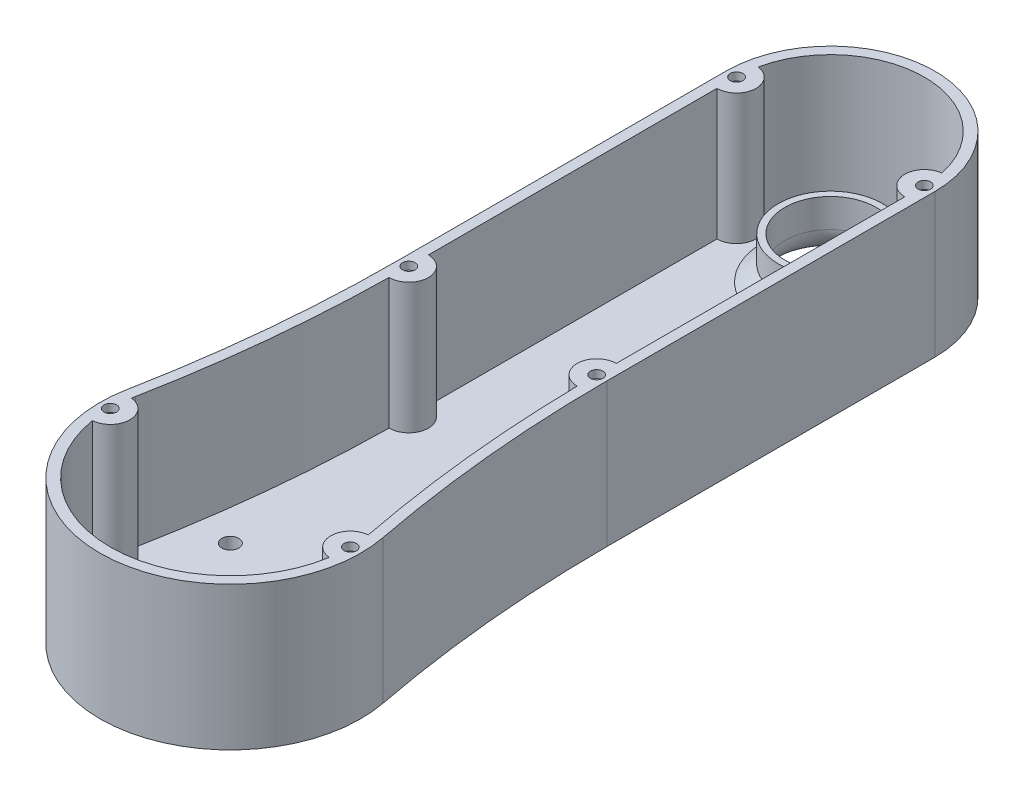
SolidWorks part; units mm, degrees
ref_plane "前视基准面" through (0, 0, 0) normal (0, 0, 1) x (1, 0, 0)
ref_plane "上视基准面" through (0, 0, 0) normal (0, 1, 0) x (1, 0, 0)
ref_plane "右视基准面" through (0, 0, 0) normal (1, 0, 0) x (0, 0, -1)
other "Configuration Table"
sketch "草图1" plane through (0, 0, 0) normal (0, 1, 0) x (1, 0, 0)
  line L0 (0, 0) -> (0, 50000) construction
  line L4 (40, 230) -> (40, 104.4031)
  line L6 (-40, 230) -> (-40, 104.4031)
  arc A8 (-49.0909, 9.4912) -> (49.0909, 9.4912) centre (0, 0) ccw
  arc A9 (40, 230) -> (-40, 230) centre (0, 230) ccw
  arc A10 (40, 104.4031) -> (49.0909, 9.4912) centre (540, 104.4031) ccw
  arc A11 (-40, 104.4031) -> (-49.0909, 9.4912) centre (-540, 104.4031) cw
  point P10 (0, 30)
  point P11 (40, 30)
  point P14 (-40, 30)
  dimension "D1" = 100
  dimension "D4" = 40
  dimension "D5" = 500
  dimension "D2" = 40
  dimension "D3" = 200
extrude "凸台-拉伸1" add sketch "草图1" along normal blind 5
sketch "草图2" plane through (0, 5, 0) normal (0, 1, 0) x (1, 0, 0)
  circle A0 centre (28.2843, 28.2843) radius 3.25
  circle A1 centre (28.2843, -28.2843) radius 3.25
  circle A2 centre (-28.2843, -28.2843) radius 3.25
  circle A3 centre (-28.2843, 28.2843) radius 3.25
  point P12 (0, 0)
  dimension "D1" = 6.5
  dimension "D2" = 4
extrude "切除-拉伸1" cut sketch "草图2" against normal blind 5
sketch "草图3" plane through (0, 5, 0) normal (0, 1, 0) x (1, 0, 0)
  line L9 (40, 104.4031) -> (40, 230)
  line L10 (-40, 230) -> (-40, 104.4031)
  line L11 (36, 104.4031) -> (36, 230)
  line L12 (-36, 230) -> (-36, 104.4031)
  line L13 (36, 111.9031) -> (36, 222.5)
  line L14 (-36, 222.5) -> (-36, 111.9031)
  line L15 (0, 230) -> (0, -49770) construction
  line L16 (-36, 230) -> (-36, 104.4031) construction
  line L17 (36, 104.4031) -> (36, 230) construction
  arc A12 (40, 230) -> (-40, 230) centre (0, 230) ccw
  arc A13 (-49.0909, 9.4912) -> (-40, 104.4031) centre (-540, 104.4031) ccw
  arc A14 (-49.0909, 9.4912) -> (49.0909, 9.4912) centre (0, 0) ccw
  arc A15 (40, 104.4031) -> (49.0909, 9.4912) centre (540, 104.4031) ccw
  arc A16 (-45.1636, 8.7319) -> (45.1636, 8.7319) centre (0, 0) ccw
  arc A17 (-45.1636, 8.7319) -> (-36, 104.4031) centre (-540, 104.4031) ccw
  arc A18 (36, 104.4031) -> (45.1636, 8.7319) centre (540, 104.4031) ccw
  arc A19 (36, 230) -> (-36, 230) centre (0, 230) ccw
  arc A20 (-45.1636, 8.7319) -> (-45.3886, 7.475) centre (0, 0) ccw
  arc A21 (-45.1636, 8.7319) -> (-36.0558, 96.9033) centre (-540, 104.4031) ccw
  arc A22 (36.0558, 96.9033) -> (45.1636, 8.7319) centre (540, 104.4031) ccw
  arc A23 (35.2187, 237.4592) -> (-35.2187, 237.4592) centre (0, 230) ccw
  arc A24 (-36, 222.5) -> (-35.2187, 237.4592) centre (-36, 230) ccw
  arc A25 (-36.0558, 96.9033) -> (-36, 111.9031) centre (-36, 104.4031) ccw
  arc A26 (-45.3886, -7.475) -> (-45.3886, 7.475) centre (-46, 0) ccw
  arc A29 (36, 222.5) -> (35.2187, 237.4592) centre (36, 230) cw
  arc A30 (36, 230) -> (-36, 230) centre (0, 230) ccw construction
  arc A31 (-45.1636, 8.7319) -> (-36, 104.4031) centre (-540, 104.4031) ccw construction
  arc A32 (-45.3886, -7.475) -> (45.3886, -7.475) centre (0, 0) ccw
  arc A33 (-45.1636, 8.7319) -> (45.1636, 8.7319) centre (0, 0) ccw construction
  arc A34 (45.3886, 7.475) -> (45.1636, 8.7319) centre (0, 0) ccw
  arc A35 (45.3886, -7.475) -> (45.3886, 7.475) centre (46, 0) cw
  arc A36 (36, 104.4031) -> (45.1636, 8.7319) centre (540, 104.4031) ccw construction
  arc A37 (36.0558, 96.9033) -> (36, 111.9031) centre (36, 104.4031) cw
  dimension "D3" = 15
  dimension "D4" = 500
  dimension "D5" = 15
  dimension "D6" = 15
  dimension "D1" = 4
  dimension "D2" = 4
extrude "凸台-拉伸2" add sketch "草图3" along normal blind 50
sketch "草图4" plane through (0, 55, 0) normal (0, 1, 0) x (1, 0, 0)
  line L0 (0, 270) -> (0, -49730) construction
  circle A0 centre (36, 230) radius 2.4
  arc A1 (40, 230) -> (-40, 230) centre (0, 230) ccw construction
  circle A2 centre (36, 104.4031) radius 2.4
  circle A3 centre (46, 0) radius 2.4
  circle A4 centre (-46, 0) radius 2.4
  circle A5 centre (-36, 104.4031) radius 2.4
  circle A6 centre (-36, 230) radius 2.4
  point P8 (0, 270)
  dimension "D1" = 4.8
  dimension "D2" = 4.8
  dimension "D3" = 4.8
extrude "切除-拉伸2" cut sketch "草图4" against normal blind 3
sketch "草图5" plane through (0, 5, 0) normal (0, 1, 0) x (1, 0, 0)
  circle A0 centre (0, 230) radius 17.5
  dimension "D1" = 35
extrude "切除-拉伸3" cut sketch "草图5" against normal blind 51
sketch "草图7" plane through (0, 5, 0) normal (0, 1, 0) x (1, 0, 0)
  circle A0 centre (0, 230) radius 20
  circle A1 centre (0, 230) radius 17.5
  dimension "D1" = 40
  dimension "D2" = 35
extrude "凸台-拉伸3" add sketch "草图7" along normal blind 16
chamfer "倒角1" distance 6 angle 45 1 edges at (0, 5, -210)
fillet "圆角3" radius 10 1 edges at (0, 0, -212.5)
